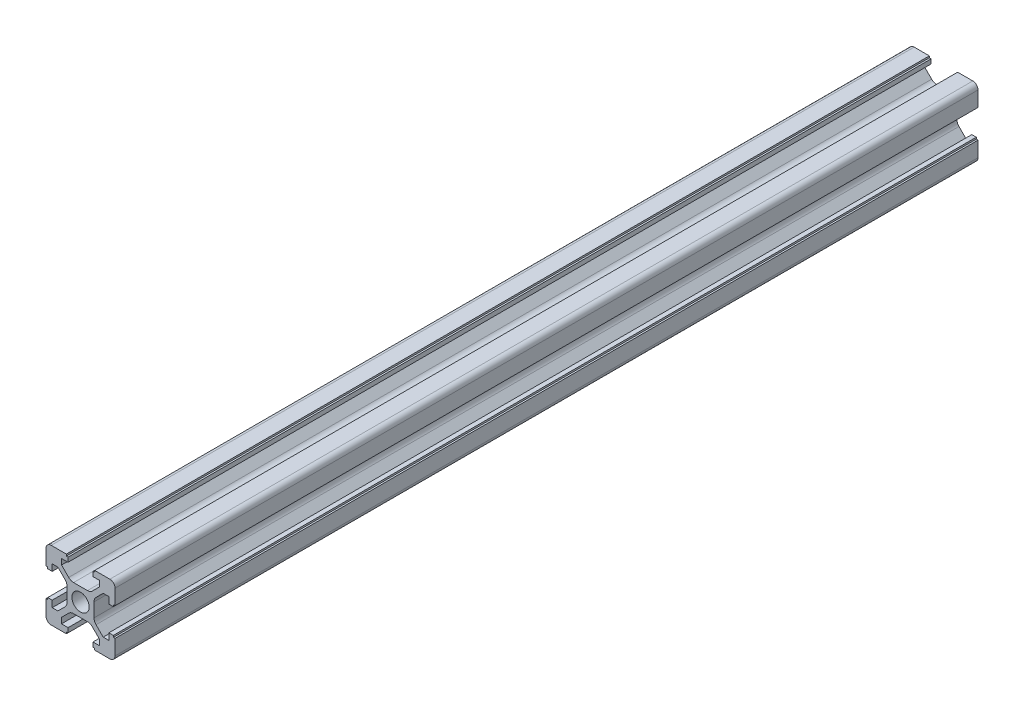
SolidWorks part; units mm, degrees
material "6063-O"
ref_plane "Front Plane" through (0, 0, 0) normal (0, 0, 1) x (1, 0, 0)
ref_plane "Top Plane" through (0, 0, 0) normal (0, 1, 0) x (1, 0, 0)
ref_plane "Right Plane" through (0, 0, 0) normal (1, 0, 0) x (0, 0, -1)
sketch "Sketch1" plane through (0, 0, 0) normal (0, 0, 1) x (1, 0, 0)
  line L0 (10, -4.1) -> (10, -8.5)
  line L1 (4.1, 10) -> (8.5, 10)
  line L2 (8.5, -10) -> (4.1, -10)
  line L3 (-8.5, -10) -> (-4.1, -10)
  line L4 (10, 8.5) -> (10, 4.1)
  line L7 (8.5, 10) -> (4.1, 10)
  line L8 (5.5, 6.5607) -> (3.4251, 4.4858)
  line L9 (8.5, 10) -> (4.1, 10)
  line L10 (3.9, 2.0109) -> (3.9, -2.0109)
  line L11 (2.0109, -3.9) -> (-2.0109, -3.9)
  line L12 (-3.9, -2.0109) -> (-3.9, 2.0109)
  line L13 (-2.0109, 3.9) -> (2.8393, 3.9)
  line L14 (2.5, 0) -> (22.2403, 0) construction
  line L15 (3.6, 9.5) -> (3.6, 8.2)
  line L16 (9.5, 3.6) -> (8.2, 3.6)
  line L17 (8.2, 3.6) -> (8.2, 5.5)
  line L18 (8.2, 5.5) -> (6.5607, 5.5)
  line L19 (10, -4.1) -> (10, -8.5)
  line L20 (4.1, 9.5) -> (3.6, 9.5)
  line L21 (4.1, 10) -> (4.1, 9.5)
  line L22 (8.5, 10) -> (4.1, 10)
  line L23 (10, 4.1) -> (9.5, 4.1)
  line L24 (9.5, 4.1) -> (9.5, 3.6)
  line L25 (5.5, 8.2) -> (5.5, 6.5607)
  line L26 (3.6, 8.2) -> (5.5, 8.2)
  line L27 (4.4858, 3.4251) -> (6.5607, 5.5)
  line L28 (10, -8.5) -> (10, -4.1)
  line L29 (6.5607, -5.5) -> (4.4858, -3.4251)
  line L30 (10, -8.5) -> (10, -4.1)
  line L31 (2.0109, -3.9) -> (-2.0109, -3.9)
  line L32 (3.9, 2.8393) -> (3.9, -2.0109)
  line L33 (9.5, -3.6) -> (8.2, -3.6)
  line L34 (3.6, -9.5) -> (3.6, -8.2)
  line L35 (3.6, -8.2) -> (5.5, -8.2)
  line L36 (5.5, -8.2) -> (5.5, -6.5607)
  line L37 (9.5, -4.1) -> (9.5, -3.6)
  line L38 (10, -4.1) -> (9.5, -4.1)
  line L39 (10, -8.5) -> (10, -4.1)
  line L40 (4.1, -10) -> (4.1, -9.5)
  line L41 (4.1, -9.5) -> (3.6, -9.5)
  line L42 (8.2, -5.5) -> (6.5607, -5.5)
  line L43 (8.2, -3.6) -> (8.2, -5.5)
  line L44 (3.4251, -4.4858) -> (5.5, -6.5607)
  line L45 (-4.1, -10) -> (-8.5, -10)
  line L46 (-10, -8.5) -> (-10, -4.1)
  line L47 (-8.5, -10) -> (-4.1, -10)
  line L48 (-5.5, -6.5607) -> (-3.4251, -4.4858)
  line L49 (-8.5, -10) -> (-4.1, -10)
  line L50 (-3.9, -2.0109) -> (-3.9, 2.0109)
  line L51 (2.0109, -3.9) -> (-2.0109, -3.9)
  line L52 (-3.6, -9.5) -> (-3.6, -8.2)
  line L53 (-9.5, -3.6) -> (-8.2, -3.6)
  line L54 (-8.2, -3.6) -> (-8.2, -5.5)
  line L55 (-8.2, -5.5) -> (-6.5607, -5.5)
  line L56 (-4.1, -9.5) -> (-3.6, -9.5)
  line L57 (-4.1, -10) -> (-4.1, -9.5)
  line L58 (-8.5, -10) -> (-4.1, -10)
  line L59 (-10, -4.1) -> (-9.5, -4.1)
  line L60 (-9.5, -4.1) -> (-9.5, -3.6)
  line L61 (-5.5, -8.2) -> (-5.5, -6.5607)
  line L62 (-3.6, -8.2) -> (-5.5, -8.2)
  line L63 (-4.4858, -3.4251) -> (-6.5607, -5.5)
  line L64 (-10, 4.1) -> (-10, 8.5)
  line L65 (-8.5, 10) -> (-4.1, 10)
  line L66 (-10, 8.5) -> (-10, 4.1)
  line L67 (-6.5607, 5.5) -> (-4.4858, 3.4251)
  line L68 (-10, 8.5) -> (-10, 4.1)
  line L69 (-2.0109, 3.9) -> (2.0109, 3.9)
  line L70 (-3.9, -2.0109) -> (-3.9, 2.0109)
  line L71 (-9.5, 3.6) -> (-8.2, 3.6)
  line L72 (-3.6, 9.5) -> (-3.6, 8.2)
  line L73 (-3.6, 8.2) -> (-5.5, 8.2)
  line L74 (-5.5, 8.2) -> (-5.5, 6.5607)
  line L75 (-9.5, 4.1) -> (-9.5, 3.6)
  line L76 (-10, 4.1) -> (-9.5, 4.1)
  line L77 (-10, 8.5) -> (-10, 4.1)
  line L78 (-4.1, 10) -> (-4.1, 9.5)
  line L79 (-4.1, 9.5) -> (-3.6, 9.5)
  line L80 (-8.2, 5.5) -> (-6.5607, 5.5)
  line L81 (-8.2, 3.6) -> (-8.2, 5.5)
  line L82 (-3.4251, 4.4858) -> (-5.5, 6.5607)
  line L83 (4.1, -10) -> (8.5, -10)
  arc A0 (2.0109, -3.9) -> (3.4251, -4.4858) centre (2.0109, -5.9) cw
  arc A1 (4.4858, -3.4251) -> (3.9, -2.0109) centre (5.9, -2.0109) cw
  arc A2 (3.9, 2.0109) -> (4.4858, 3.4251) centre (5.9, 2.0109) cw
  arc A3 (2.0109, 3.9) -> (3.4251, 4.4858) centre (2.0109, 5.9) ccw
  arc A4 (-2.0109, 3.9) -> (-3.4251, 4.4858) centre (-2.0109, 5.9) cw
  arc A5 (-4.4858, 3.4251) -> (-3.9, 2.0109) centre (-5.9, 2.0109) cw
  arc A6 (-3.4251, -4.4858) -> (-2.0109, -3.9) centre (-2.0109, -5.9) cw
  arc A7 (-3.9, -2.0109) -> (-4.4858, -3.4251) centre (-5.9, -2.0109) cw
  circle A8 centre (0, 0) radius 2.5
  arc A9 (-8.5, -10) -> (-10, -8.5) centre (-8.5, -8.5) cw
  arc A10 (-10, 8.5) -> (-8.5, 10) centre (-8.5, 8.5) cw
  arc A11 (8.5, 10) -> (10, 8.5) centre (8.5, 8.5) cw
  arc A12 (8.5, -10) -> (10, -8.5) centre (8.5, -8.5) ccw
  point P0 (0, 0)
  point P86 (0, 0)
  point P107 (10, -10)
  dimension "D3" = 2
  dimension "D5" = 5
  dimension "D2" = 1.5
  dimension "D8" = 1.5
  dimension "D6" = 4
  dimension "D7" = 6.1
  dimension "D11" = 0.5
  dimension "D12" = 0.5
extrude "Boss-Extrude2" add sketch "Sketch1" along normal blind 250 contours L2 A12 L0 L38 L37 L33 L43 L42 L29 A1 L10 A2 L27 L18 L17 L16 L24 L23 L4 A11 L1 L21 L20 L15 L26 L25 L8 A3 L13 A4 L82 L74 L73 L72 L79 L78 L65 A10 L64 L76 L75 L71 L81 L80 L67 A5 L12 region at (9.7172, -6.3, 0)
